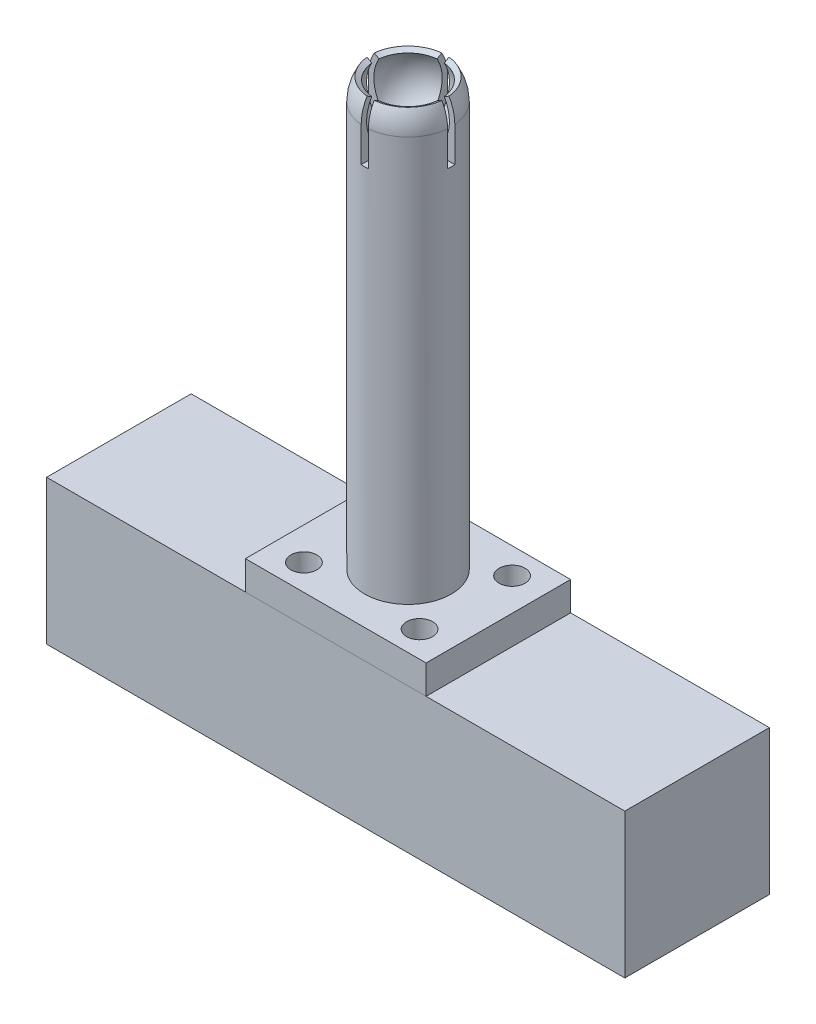
SolidWorks part; units mm, degrees
ref_plane "Front Plane" through (0, 0, 0) normal (0, 0, 1) x (1, 0, 0)
ref_plane "Top Plane" through (0, 0, 0) normal (0, 1, 0) x (1, 0, 0)
ref_plane "Right Plane" through (0, 0, 0) normal (1, 0, 0) x (0, 0, -1)
sketch "Sketch1" plane through (0, 0, 0) normal (0, 1, 0) x (1, 0, 0)
  line L1 (-50.8, 12.7) -> (50.8, 12.7)
  line L2 (-50.8, 12.7) -> (-50.8, -12.7)
  line L3 (-50.8, -12.7) -> (50.8, -12.7)
  line L4 (50.8, 12.7) -> (50.8, -12.7)
  line L5 (-50.8, 12.7) -> (50.8, -12.7) construction
  line L6 (-50.8, -12.7) -> (50.8, 12.7) construction
  point P0 (0, 0)
  dimension "D1" = 101.6
  dimension "D2" = 25.4
extrude "Boss-Extrude1" add sketch "Sketch1" along normal blind 25.4
sketch "Sketch2" plane through (0, 25.4, 0) normal (0, 1, 0) x (1, 0, 0)
  line L0 (-50.8, -12.7) -> (50.8, -12.7) construction
  line L1 (-15.875, 12.7) -> (15.875, 12.7)
  line L2 (-15.875, 12.7) -> (-15.875, -12.7)
  line L3 (-15.875, -12.7) -> (15.875, -12.7)
  line L4 (15.875, 12.7) -> (15.875, -12.7)
  line L5 (-15.875, 12.7) -> (15.875, -12.7) construction
  line L6 (-15.875, -12.7) -> (15.875, 12.7) construction
  circle A0 centre (10.16, -8.128) radius 2.286
  circle A1 centre (-10.16, -8.128) radius 2.286
  circle A2 centre (-10.16, 8.128) radius 2.286
  circle A3 centre (10.16, 8.128) radius 2.286
  point P0 (0, 0)
  point P16 (0, 0)
  point P17 (0, 0)
  point P18 (0, 0)
  dimension "D2" = 4.572
  dimension "D1" = 31.75
  dimension "D3" = 10.16
extrude "Boss-Extrude2" add sketch "Sketch2" along normal blind 5.08 separate body
sketch "Sketch3" plane through (0, 30.48, 0) normal (0, 1, 0) x (1, 0, 0)
  circle A0 centre (0, 0) radius 7.62
  dimension "D1" = 15.24
extrude "Boss-Extrude3" add sketch "Sketch3" along normal blind 63.5
sketch "Sketch4" plane through (0, 0, 0) normal (0, 0, 1) x (1, 0, 0)
  line L0 (7.62, 93.98) -> (-7.62, 93.98) construction
  line L1 (7.62, 93.98) -> (-7.62, 93.98)
  line L2 (-7.62, 93.98) -> (-7.62, 101.6)
  line L4 (0, 93.98) -> (0, 94.9325)
  line L5 (-5.7742, 104.9337) -> (-6.5991, 105.41)
  line L6 (-5.7742, 104.9337) -> (0, 101.6) construction
  arc A0 (-6.5991, 105.41) -> (-7.62, 101.6) centre (0, 101.6) ccw
  arc A1 (-5.7742, 104.9337) -> (0, 94.9325) centre (0, 101.6) ccw
  point P6 (0, 93.98)
  point P9 (-5.3882, 106.9882)
  dimension "D1" = 15.24
  dimension "D2" = 13.335
  dimension "D3" = 60
revolve "Revolve1" add sketch "Sketch4" angle 360 about axis through (0, 93.98, 0) along (0, -1, 0) region at (-5.4943, 97.2611, 0)
ref_plane "Plane1" through (0, 105.41, 0) normal (0, 1, 0) x (1, 0, 0)
sketch "Sketch5" plane through (0, 105.41, 0) normal (0, 1, 0) x (1, 0, 0)
  line L1 (8.89, -0.635) -> (-8.89, -0.635)
  line L2 (8.89, -0.635) -> (8.89, 0.635)
  line L3 (8.89, 0.635) -> (-8.89, 0.635)
  line L4 (-8.89, -0.635) -> (-8.89, 0.635)
  line L5 (8.89, -0.635) -> (-8.89, 0.635) construction
  line L6 (8.89, 0.635) -> (-8.89, -0.635) construction
  line L7 (0.635, 8.89) -> (-0.635, 8.89)
  line L8 (0.635, 8.89) -> (0.635, -8.89)
  line L9 (0.635, -8.89) -> (-0.635, -8.89)
  line L10 (-0.635, 8.89) -> (-0.635, -8.89)
  line L11 (0.635, 8.89) -> (-0.635, -8.89) construction
  line L12 (0.635, -8.89) -> (-0.635, 8.89) construction
  point P0 (0, 0)
  point P6 (0, 0)
  dimension "D1" = 17.78
  dimension "D2" = 1.27
extrude "Cut-Extrude2" cut sketch "Sketch5" against normal blind 9.906 contours L1 L10 L9 L8 | L7 L10 L3 L8 | L3 L8 L1 L2 | L10 L3 L4 L1 | L3 L10 L1 L8 region at (4.7625, 105.41, 0) region at (0, 105.41, 4.7625) region at (0, 105.41, 0) region at (-4.7625, 105.41, 0) region at (0, 105.41, -4.7625)
